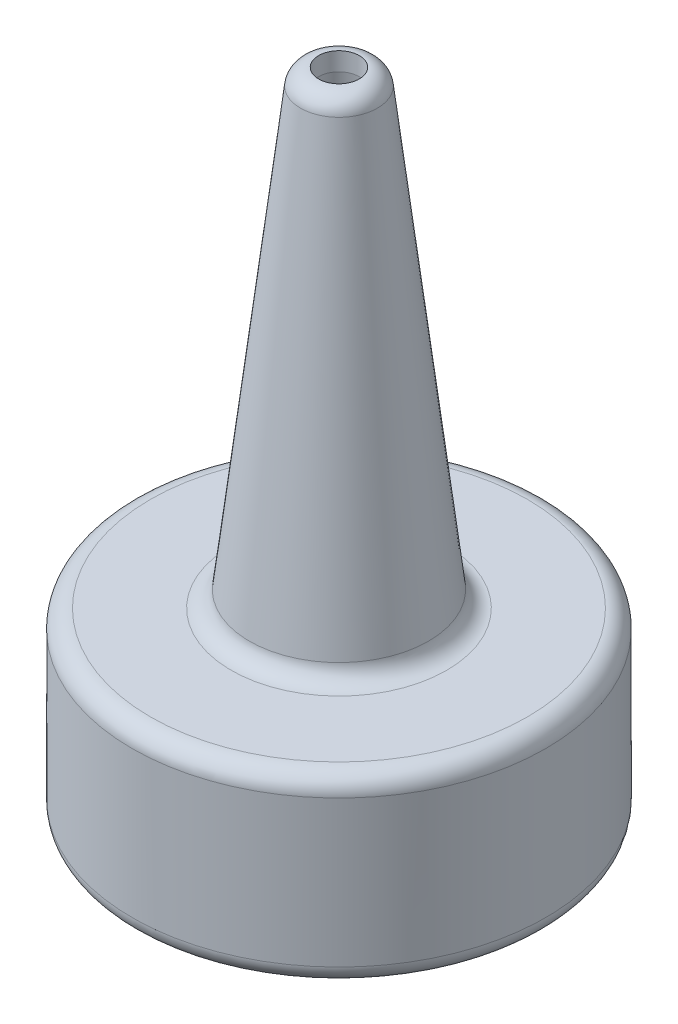
SolidWorks part; units mm, degrees
ref_plane "Front Plane" through (0, 0, 0) normal (0, 0, 1) x (1, 0, 0)
ref_plane "Top Plane" through (0, 0, 0) normal (0, 1, 0) x (1, 0, 0)
ref_plane "Right Plane" through (0, 0, 0) normal (1, 0, 0) x (0, 0, -1)
sketch "Sketch1" plane through (0, 0, 0) normal (0, 0, 1) x (1, 0, 0)
  line L0 (13.081, 0) -> (14.351, 0)
  line L1 (14.351, 0) -> (14.351, 12.7)
  line L2 (14.351, 12.7) -> (6.35, 12.7)
  line L3 (6.35, 12.7) -> (2.54, 45.212)
  line L4 (2.54, 45.212) -> (1.4101, 45.212)
  line L5 (0, 43.942) -> (0, 1.27) construction
  line L6 (5.2201, 11.43) -> (1.4101, 43.942)
  line L7 (0, 45.212) -> (0, 0) construction
  line L8 (13.081, 1.27) -> (13.081, 0)
  line L10 (13.081, 1.27) -> (13.081, 11.43)
  line L11 (13.081, 11.43) -> (5.2201, 11.43)
  line L12 (1.4101, 43.942) -> (1.4101, 45.212)
  line L15 (1.27, 43.942) -> (1.27, 1.27) construction
  line L16 (2.54, 45.212) -> (0, 45.212) construction
  line L17 (1.4101, 43.942) -> (1.27, 43.942) construction
  line L18 (0, 0) -> (14.351, 0) construction
  line L19 (1.27, 1.27) -> (13.081, 1.27) construction
  dimension "D2" = 12.7
  dimension "D4" = 6.35
  dimension "D6" = 1.27
revolve "Revolve1" add sketch "Sketch1" angle 360 about L5
fillet "Fillet1" radius 1.27 4 edges at (-2.54, 45.212, 0) (-14.351, 0, 0) (-6.35, 12.7, 0) (-14.351, 12.7, 0)
